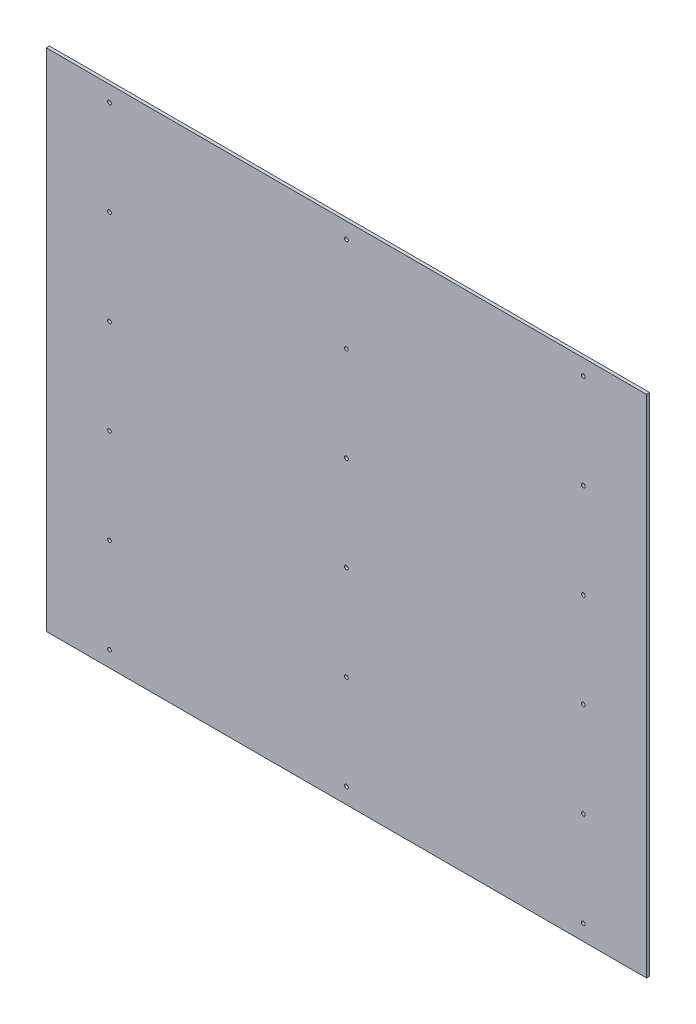
SolidWorks part; units mm, degrees
ref_plane "Płaszczyzna przednia" through (0, 0, 0) normal (0, 0, 1) x (1, 0, 0)
ref_plane "Płaszczyzna górna" through (0, 0, 0) normal (0, 1, 0) x (1, 0, 0)
ref_plane "Płaszczyzna prawa" through (0, 0, 0) normal (1, 0, 0) x (0, 0, -1)
sketch "Szkic1" plane through (0, 0, 0) normal (0, 0, 1) x (1, 0, 0)
  line L1 (-950, -800) -> (950, -800)
  line L2 (-950, -800) -> (-950, 800)
  line L3 (-950, 800) -> (950, 800)
  line L4 (950, -800) -> (950, 800)
  line L5 (-950, -800) -> (950, 800) construction
  line L6 (-950, 800) -> (950, -800) construction
  point P0 (0, 0)
  dimension "D1" = 1900
  dimension "D2" = 1600
extrude "Dodanie-wyciągnięcie1" add sketch "Szkic1" along normal blind 10
hole_wizard "Otwór pod śrubę M101" positions "Szkic2" profile "Szkic3" hole size "M10" standard "Ansi Metric" end condition through all
sketch "Szkic2" plane through (0, 0, 10) normal (0, 0, 1) x (1, 0, 0)
  line L0 (-950, 800) -> (-950, -800) construction
  line L2 (-950, -800) -> (950, -800) construction
  point P0 (-750, -750)
  dimension "D1" = 200
  dimension "D2" = 50
sketch "Szkic3" plane through (-750, -750, 10) normal (1, 0, 0) x (0, -1, 0)
  line L0 (0, 0) -> (0, 10)
  line L1 (0, 10) -> (6, 10)
  line L2 (6, 10) -> (6, 0)
  line L5 (6, 0) -> (0, 0)
  line L11 (0, -6.35) -> (0, 107.95) construction
  dimension "Średnica otworu na wylot" = 12
  dimension "Głębokość otworu na wylot" = 10
pattern_linear "Szyk liniowy1" count 6 spacing 300 along (0, 1, 0) count 3 spacing 750 along (1, 0, 0) of "Otwór pod śrubę M101"
